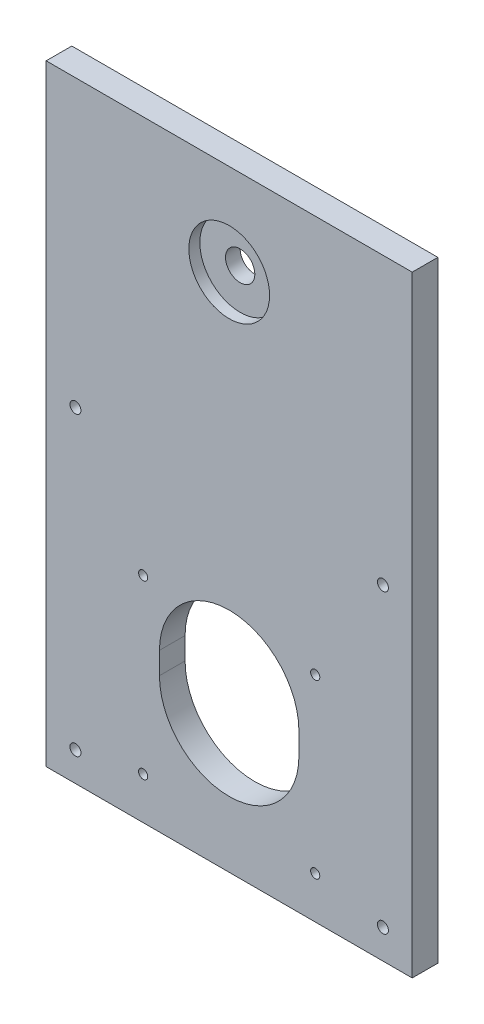
SolidWorks part; units mm, degrees
ref_plane "Front Plane" through (0, 0, 0) normal (0, 0, 1) x (1, 0, 0)
ref_plane "Top Plane" through (0, 0, 0) normal (0, 1, 0) x (1, 0, 0)
ref_plane "Right Plane" through (0, 0, 0) normal (1, 0, 0) x (0, 0, -1)
sketch "Sketch1" plane through (0, 0, 0) normal (0, 0, 1) x (1, 0, 0)
  line L1 (-50, 123.5) -> (50, 123.5)
  line L2 (-50, 123.5) -> (-50, -123.5)
  line L3 (-50, -123.5) -> (50, -123.5)
  line L4 (50, 123.5) -> (50, -123.5)
  line L5 (-50, 123.5) -> (50, -123.5) construction
  line L6 (-50, -123.5) -> (50, 123.5) construction
  line L8 (-19.05, -80.5) -> (-19.05, -86.5)
  line L9 (19.05, -86.5) -> (19.05, -80.5)
  line L10 (-23.5, -55) -> (-23.5, -65) construction
  line L14 (-22.25, -55) -> (-22.25, -65) construction
  line L15 (-24.75, -55) -> (-24.75, -65) construction
  line L16 (0, -83.5) -> (41.1398, -83.5) construction
  line L17 (0, -83.5) -> (0, -119.2312) construction
  line L18 (23.5, -55) -> (23.5, -65) construction
  line L19 (22.25, -55) -> (22.25, -65) construction
  line L20 (24.75, -55) -> (24.75, -65) construction
  line L21 (23.5, -112) -> (23.5, -102) construction
  line L22 (22.25, -112) -> (22.25, -102) construction
  line L23 (24.75, -112) -> (24.75, -102) construction
  line L24 (-23.5, -112) -> (-23.5, -102) construction
  line L25 (-22.25, -112) -> (-22.25, -102) construction
  line L26 (-24.75, -112) -> (-24.75, -102) construction
  circle A0 centre (-42, -34.5) radius 1.5
  circle A1 centre (42, -34.5) radius 1.5
  circle A2 centre (-42, -115.5) radius 1.5
  circle A3 centre (42, -115.5) radius 1.5
  arc A6 (19.05, -80.5) -> (-19.05, -80.5) centre (0, -80.5) ccw
  arc A7 (-19.05, -86.5) -> (19.05, -86.5) centre (0, -86.5) ccw
  arc A10 (-22.25, -55) -> (-24.75, -55) centre (-23.5, -55) ccw construction
  arc A11 (-24.75, -65) -> (-22.25, -65) centre (-23.5, -65) ccw construction
  arc A12 (22.25, -55) -> (24.75, -55) centre (23.5, -55) cw construction
  arc A13 (24.75, -65) -> (22.25, -65) centre (23.5, -65) cw construction
  arc A14 (22.25, -112) -> (24.75, -112) centre (23.5, -112) ccw construction
  arc A15 (24.75, -102) -> (22.25, -102) centre (23.5, -102) ccw construction
  arc A16 (-22.25, -112) -> (-24.75, -112) centre (-23.5, -112) cw construction
  arc A17 (-24.75, -102) -> (-22.25, -102) centre (-23.5, -102) cw construction
  circle A18 centre (0, 18.5) radius 4
  circle A19 centre (42, 115.5) radius 1.5
  circle A20 centre (-42, 115.5) radius 1.5
  circle A21 centre (-14, 32.5) radius 2.625 construction
  circle A22 centre (14, 32.5) radius 2.625 construction
  circle A23 centre (14, 4.5) radius 2.625 construction
  circle A24 centre (-14, 4.5) radius 2.625 construction
  circle A25 centre (-23.5, -65) radius 1.25
  circle A26 centre (-23.5, -112) radius 1.25
  circle A27 centre (23.5, -112) radius 1.25
  circle A28 centre (23.5, -65) radius 1.25
  point P0 (0, 0)
  point P14 (-23.5, -60)
  point P17 (0, -83.5)
  point P34 (23.5, -60)
  point P41 (23.5, -107)
  point P48 (-23.5, -107)
  dimension "D3" = 3
  dimension "D4" = 81
  dimension "D6" = 2.5
  dimension "D8" = 8
  dimension "D12" = 19.05
  dimension "D14" = 3
  dimension "D15" = 23.5
  dimension "D16" = 8
  dimension "D19" = 5.25
  dimension "D1" = 100
  dimension "D2" = 247
  dimension "D5" = 84
  dimension "D7" = 10
  dimension "D9" = 6
  dimension "D10" = 8
  dimension "D11" = 23.5
  dimension "D17" = 105
  dimension "D18" = 8
  dimension "D20" = 28
  dimension "D21" = 28
  dimension "D22" = 14
  dimension "D23" = 14
  dimension "D24" = 83.5
extrude "Boss-Extrude1" add sketch "Sketch1" along normal blind 7
sketch "Sketch2" plane through (0, 0, 7) normal (0, 0, 1) x (1, 0, 0)
  circle A0 centre (0, 18.5) radius 11.025
  dimension "D1" = 22.05
extrude "Cut-Extrude1" cut sketch "Sketch2" against normal blind 3
sketch "Sketch3" plane through (0, 0, 0) normal (0, 0, 1) x (1, 0, 0)
  line L0 (-23.5, -70) -> (-23.5, -60) construction
  line L1 (-26.5, -70) -> (-26.5, -60)
  line L2 (-20.5, -70) -> (-20.5, -60)
  line L3 (23.5, -70) -> (23.5, -60) construction
  line L4 (20.5, -70) -> (20.5, -60)
  line L5 (26.5, -70) -> (26.5, -60)
  line L6 (-23.5, -117) -> (-23.5, -107) construction
  line L7 (-26.5, -117) -> (-26.5, -107)
  line L8 (-20.5, -117) -> (-20.5, -107)
  line L9 (23.5, -117) -> (23.5, -107) construction
  line L10 (20.5, -117) -> (20.5, -107)
  line L11 (26.5, -117) -> (26.5, -107)
  arc A0 (-26.5, -70) -> (-20.5, -70) centre (-23.5, -70) ccw
  arc A1 (-20.5, -60) -> (-26.5, -60) centre (-23.5, -60) ccw
  arc A2 (20.5, -70) -> (26.5, -70) centre (23.5, -70) ccw
  arc A3 (26.5, -60) -> (20.5, -60) centre (23.5, -60) ccw
  arc A4 (-26.5, -117) -> (-20.5, -117) centre (-23.5, -117) ccw
  arc A5 (-20.5, -107) -> (-26.5, -107) centre (-23.5, -107) ccw
  arc A6 (20.5, -117) -> (26.5, -117) centre (23.5, -117) ccw
  arc A7 (26.5, -107) -> (20.5, -107) centre (23.5, -107) ccw
  point P2 (-23.5, -65)
  point P3 (-23.5, -112)
  point P4 (-23.5, -65)
  point P9 (23.5, -65)
  point P12 (23.5, -65)
  point P13 (23.5, -112)
  point P21 (-23.5, -112)
  point P29 (23.5, -112)
  point P34 (0, 0)
  point P35 (0, 0)
  point P36 (0, 0)
  point P37 (0, 0)
  point P38 (0, 0)
  point P39 (0, 0)
  point P40 (0, 0)
  dimension "D1" = 3
  dimension "D2" = 10
extrude "Cut-Extrude2" cut sketch "Sketch3" along normal blind 3
sketch "Sketch4" plane through (0, 0, 7) normal (0, 0, 1) x (1, 0, 0)
  line L0 (50, -123.5) -> (50, 123.5) construction
  line L1 (-50, 123.5) -> (50, 123.5)
  line L2 (-50, 123.5) -> (-50, 43.5)
  line L3 (-50, 43.5) -> (50, 43.5)
  line L4 (50, 123.5) -> (50, 43.5)
  line L5 (-50, 123.5) -> (50, 43.5) construction
  line L6 (-50, 43.5) -> (50, 123.5) construction
  line L7 (50, 123.5) -> (-50, 123.5) construction
  line L8 (-50, 123.5) -> (-50, -123.5) construction
  point P0 (0, 83.5)
  dimension "D1" = 80
extrude "Cut-Extrude3" cut sketch "Sketch4" against normal through all
